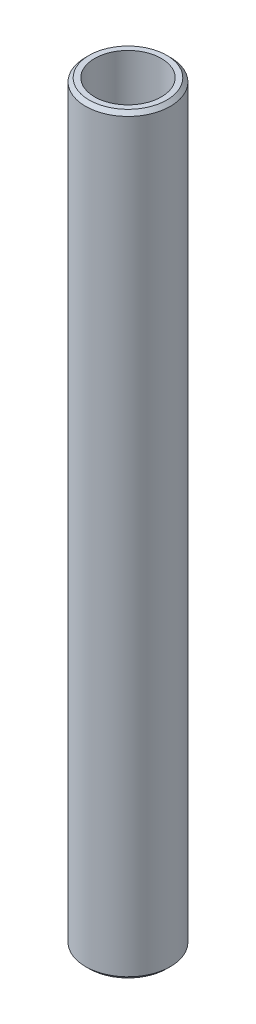
SolidWorks part; units mm, degrees
ref_plane "Front Plane" through (0, 0, 0) normal (0, 0, 1) x (1, 0, 0)
ref_plane "Top Plane" through (0, 0, 0) normal (0, 1, 0) x (1, 0, 0)
ref_plane "Right Plane" through (0, 0, 0) normal (1, 0, 0) x (0, 0, -1)
sketch "Sketch1" plane through (0, 0, 0) normal (0, 1, 0) x (1, 0, 0)
  circle A0 centre (0, 0) radius 32.5
  dimension "SHAFT_OD" = 65
extrude "Boss-Extrude1" add sketch "Sketch1" along normal blind 576.5553
sketch "Sketch2" plane through (0, 0, 0) normal (0, 1, 0) x (1, 0, 0)
  circle A0 centre (0, 0) radius 25.5768
  dimension "BORE_D" = 51.1536
extrude "Cut-Extrude1" cut sketch "Sketch2" along normal through all
chamfer "Chamfer1" distance 2.7725 angle 45 2 edges at (0, 576.5553, 32.5) (0, 0, 32.5)
